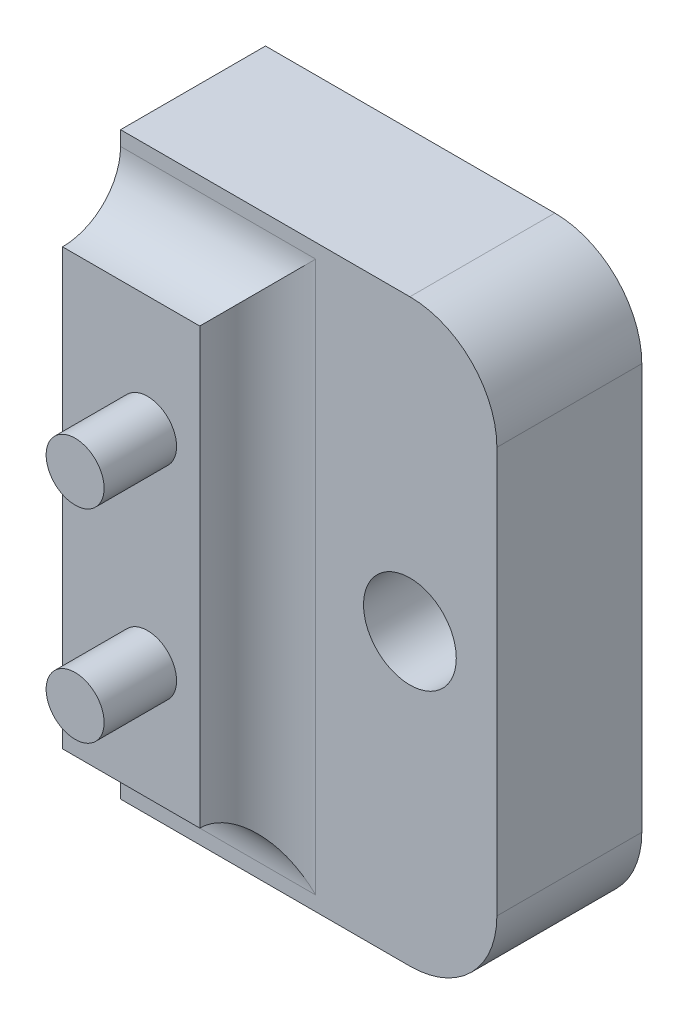
SolidWorks part; units mm, degrees
ref_plane "Alzado" through (0, 0, 0) normal (0, 0, 1) x (1, 0, 0)
ref_plane "Planta" through (0, 0, 0) normal (0, 1, 0) x (1, 0, 0)
ref_plane "Vista lateral" through (0, 0, 0) normal (1, 0, 0) x (0, 0, -1)
sketch "Croquis1" plane through (0, 0, 0) normal (0, 0, 1) x (1, 0, 0)
  line L1 (0, 0) -> (12, 0)
  line L2 (0, 0) -> (0, 20)
  line L3 (0, 20) -> (12, 20)
  line L4 (15, 3) -> (15, 17)
  circle A0 centre (12, 10) radius 1.6
  arc A1 (12, 20) -> (15, 17) centre (12, 17) cw
  arc A2 (12, 0) -> (15, 3) centre (12, 3) ccw
  point P9 (15, 20)
  dimension "D3" = 3.2
  dimension "D5" = 3
  dimension "D1" = 20
  dimension "D2" = 15
  dimension "D4" = 3
extrude "Saliente-Extruir1" add sketch "Croquis1" along normal blind 5
sketch "Croquis2" plane through (0, 0, 5) normal (0, 0, 1) x (1, 0, 0)
  line L0 (0, 20) -> (0, 0) construction
  line L1 (0, 17.5) -> (6.75, 17.5)
  line L2 (0, 17.5) -> (0, 2.5)
  line L3 (0, 2.5) -> (6.75, 2.5)
  line L4 (6.75, 17.5) -> (6.75, 2.5)
  line L5 (12, 20) -> (0, 20) construction
  dimension "D1" = 6.75
  dimension "D2" = 15
  dimension "D3" = 2.5
extrude "Saliente-Extruir2" add sketch "Croquis2" along normal blind 2
fillet "Redondeo1" radius 2 3 edges at (3.375, 17.5, 5) (6.75, 10, 5) (3.375, 2.5, 5)
sketch "Croquis3" plane through (0, 0, 7) normal (0, 0, 1) x (1, 0, 0)
  line L0 (0, 10) -> (15.8133, 10) construction
  line L2 (0, 17.5) -> (0, 2.5) construction
  circle A0 centre (4.9502, 13.5) radius 1
  circle A1 centre (4.9502, 6.5) radius 1
  dimension "D1" = 2
  dimension "D2" = 2
  dimension "D3" = 7
  dimension "D4" = 3.5
extrude "Saliente-Extruir3" add sketch "Croquis3" along normal blind 2.5
sketch "Croquis4" plane through (0, 0, 5) normal (0, 0, 1) x (1, 0, 0)
  line L1 (-4.9029, -2.6101) -> (2.0176, -2.6101)
  line L2 (-4.9029, -2.6101) -> (-4.9029, 22.3855)
  line L3 (-4.9029, 22.3855) -> (2.0176, 22.3855)
  line L4 (2.0176, -2.6101) -> (2.0176, 22.3855)
extrude "Cortar-Extruir2" cut sketch "Croquis4" against normal blind 6 and the other way blind 6
